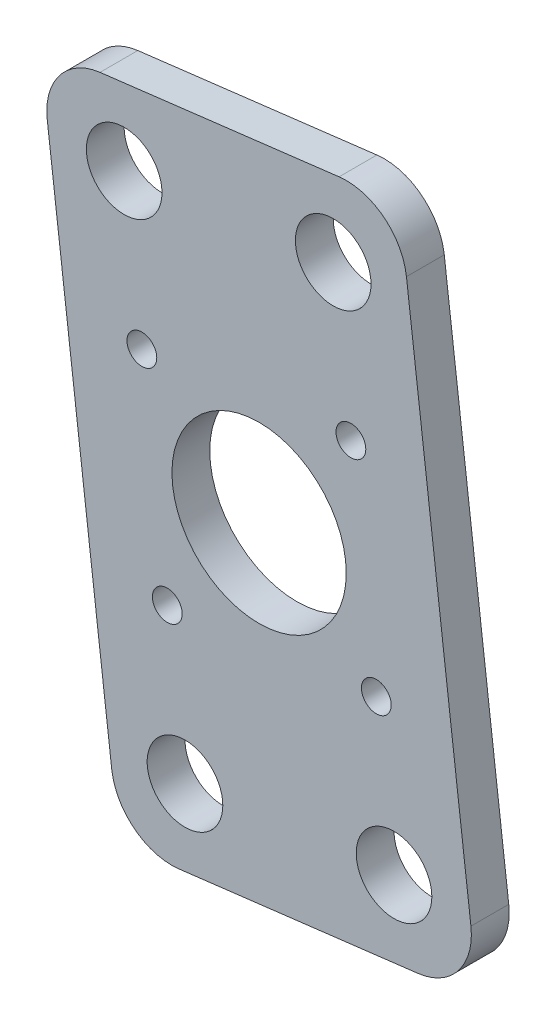
SolidWorks part; units mm, degrees
ref_plane "Front Plane" through (0, 0, 0) normal (0, 0, 1) x (1, 0, 0)
ref_plane "Top Plane" through (0, 0, 0) normal (0, 1, 0) x (1, 0, 0)
ref_plane "Right Plane" through (0, 0, 0) normal (1, 0, 0) x (0, 0, -1)
sketch "Sketch1" plane through (0, 0, 0) normal (0, 0, 1) x (1, 0, 0)
  line L12 (-108.1848, -135.7641) -> (-102.7716, -180.2793)
  line L13 (-101.7279, -136.2583) -> (-84.1795, -134.1244) construction
  line L14 (-100.2416, -148.481) -> (-82.6932, -146.3471) construction
  line L15 (-97.1156, -184.709) -> (-77.0457, -182.2684)
  line L16 (-72.6161, -176.6123) -> (-78.0293, -132.0971)
  line L17 (-83.6853, -127.6675) -> (-103.7552, -130.108)
  line L18 (-82.6932, -146.3471) -> (-80.5593, -163.8955) construction
  line L19 (-90.4004, -156.1882) -> (-93.7202, -128.8878) construction
  line L20 (-90.4004, -156.1882) -> (-87.0806, -183.4887) construction
  line L22 (-100.2416, -148.481) -> (-98.1077, -166.0294) construction
  line L23 (-98.1077, -166.0294) -> (-80.5593, -163.8955) construction
  line L24 (-101.7279, -136.2583) -> (-100.2416, -148.481) construction
  line L25 (-98.1077, -166.0294) -> (-96.6214, -178.2521) construction
  arc A0 (-97.1236, -166.8001) -> (-99.0918, -165.2587) centre (-98.1077, -166.0294) ccw
  arc A1 (-99.0918, -165.2587) -> (-97.1236, -166.8001) centre (-98.1077, -166.0294) ccw
  arc A2 (-81.5434, -163.1247) -> (-79.5752, -164.6662) centre (-80.5593, -163.8955) ccw
  arc A3 (-79.5752, -164.6662) -> (-81.5434, -163.1247) centre (-80.5593, -163.8955) ccw
  arc A4 (-81.7091, -147.1178) -> (-83.6773, -145.5763) centre (-82.6932, -146.3471) ccw
  arc A5 (-83.6773, -145.5763) -> (-81.7091, -147.1178) centre (-82.6932, -146.3471) ccw
  arc A6 (-101.2257, -147.7103) -> (-99.2575, -149.2517) centre (-100.2416, -148.481) ccw
  arc A7 (-99.2575, -149.2517) -> (-101.2257, -147.7103) centre (-100.2416, -148.481) ccw
  circle A25 centre (-101.7279, -136.2583) radius 3.175
  circle A26 centre (-84.1795, -134.1244) radius 3.175
  circle A27 centre (-79.073, -176.1182) radius 3.175
  circle A28 centre (-96.6214, -178.2521) radius 3.175
  arc A29 (-102.7716, -180.2793) -> (-97.1156, -184.709) centre (-97.7288, -179.6661) ccw
  arc A30 (-77.0457, -182.2684) -> (-72.6161, -176.6123) centre (-77.659, -177.2256) ccw
  arc A31 (-78.0293, -132.0971) -> (-83.6853, -127.6675) centre (-83.0721, -132.7103) ccw
  arc A32 (-108.1848, -135.7641) -> (-103.7552, -130.108) centre (-103.1419, -135.1509) cw
  circle A34 centre (-90.4004, -156.1882) radius 7.3172
  point P0 (-93.7202, -128.8878)
  dimension "D6" = 6.35
  dimension "D8" = 6.35
  dimension "D10" = 6.35
  dimension "D15" = 5.08
  dimension "D16" = 17.6777
  dimension "D17" = 17.6777
  dimension "D2" = 6.35
  dimension "D5" = 6.35
  dimension "D7" = 6.35
  dimension "D9" = 6.35
  dimension "D14" = 6.35
  dimension "D1" = 6.35
  dimension "D3" = 6.35
  dimension "D4" = 6.35
  dimension "D11" = 6.35
  dimension "D12" = 6.35
  dimension "D13" = 6.35
extrude "Boss-Extrude2" add sketch "Sketch1" along normal blind 3.175 contours A32 L12 A29 L15 A30 L16 A31 L17 A34 A28 A27 A26 A25 A7 A6 A5 A4 A3 A2 A1 A0 region at (-106.6113, -132.4338, 0)
